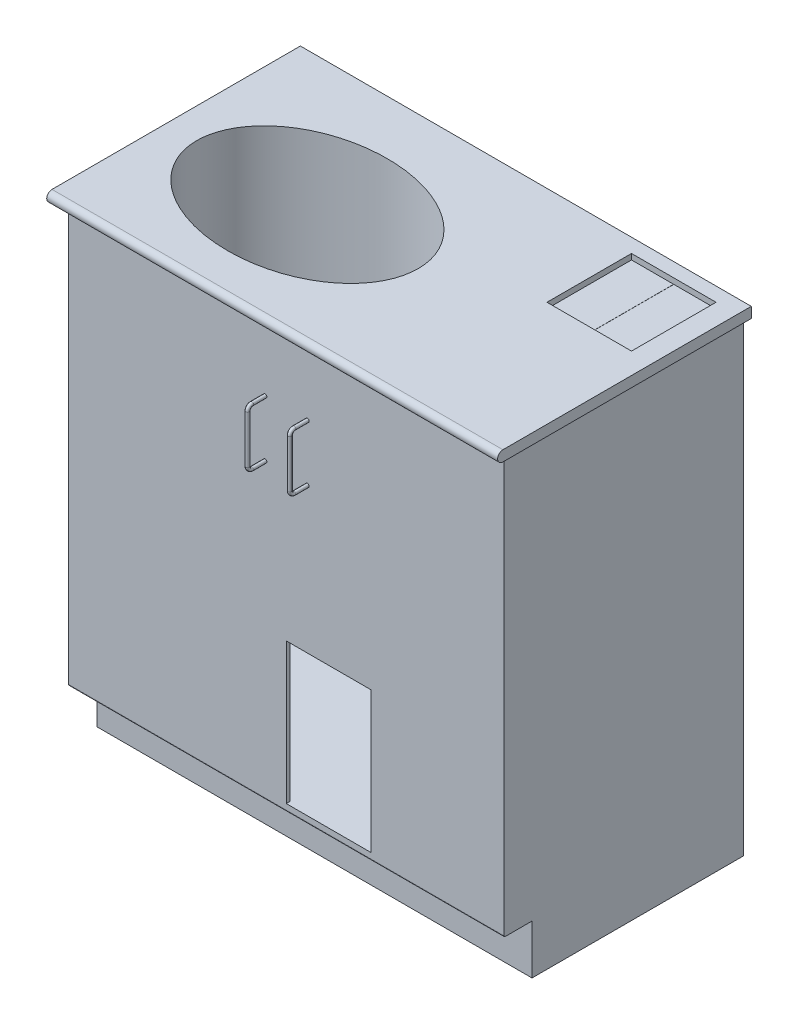
SolidWorks part; units mm, degrees
other "Camera1"
other "Camera2"
ref_plane "Front Plane" through (0, 0, 0) normal (0, 0, 1) x (1, 0, 0)
ref_plane "Top Plane" through (0, 0, 0) normal (0, 1, 0) x (1, 0, 0)
ref_plane "Right Plane" through (0, 0, 0) normal (1, 0, 0) x (0, 0, -1)
ref_plane "Ground Plane" through (0, 0, 0) normal (0, 1, 0) x (1, 0, 0)
sketch "Sketch2" plane through (0, 0, 0) normal (0, 1, 0) x (1, 0, 0)
  line L1 (0, 0) -> (812.8, 0)
  line L2 (0, 0) -> (0, 457.2)
  line L3 (0, 457.2) -> (812.8, 457.2)
  line L4 (812.8, 0) -> (812.8, 457.2)
  dimension "D1" = 812.8
  dimension "D2" = 457.2
extrude "Boss-Extrude1" add sketch "Sketch2" along normal blind 865.124
ref_plane "Wall Plane" through (0, 0, -457.2) normal (0, 0, -1) x (-1, 0, 0)
ref_plane "Faucet Plane" through (254, 0, 0) normal (-1, 0, 0) x (0, 0, 1)
ref_plane "Central Plane" through (406.4, 0, 0) normal (-1, 0, 0) x (0, 0, 1)
ref_plane "Piping Alignment" through (203.2, 0, 0) normal (-1, 0, 0) x (0, 0, 1)
sketch "Sketch28" plane through (0, 0, -457.2) normal (0, 0, -1) x (-1, 0, 0)
  line L1 (-203.2, -251.46) -> (-203.2, 251.46) construction
  circle A0 centre (-203.2, 744.0072) radius 6.35
  dimension "D1" = 0
extrude "Boss-Extrude4" add sketch "Sketch28" along normal blind 50.8
sketch "Sketch30" plane through (0, 0, -457.2) normal (0, 0, -1) x (-1, 0, 0)
  line L1 (-203.2, -251.46) -> (-203.2, 251.46) construction
  circle A0 centre (-203.2, 575.1895) radius 19.05
  dimension "D1" = 0
extrude "Boss-Extrude5" add sketch "Sketch30" along normal blind 50.8
sketch "Sketch31" plane through (812.8, 0, 0) normal (1, 0, 0) x (0, 0, -1)
  line L0 (0, 865.124) -> (0, 0) construction
  line L1 (0, 846.074) -> (25.4, 846.074)
  line L2 (0, 846.074) -> (0, 0)
  line L3 (0, 0) -> (25.4, 0)
  line L4 (25.4, 846.074) -> (25.4, 0)
  line L5 (0, 0) -> (457.2, 0) construction
  line L6 (0, 865.124) -> (457.2, 865.124) construction
  dimension "D1" = 25.4
  dimension "D2" = 19.05
extrude "Cut-Extrude1" cut sketch "Sketch31" against normal through all both and the other way through all
ref_plane "Plane2" through (368.3, 0, 0) normal (-1, 0, 0) x (0, 0, 1)
ref_plane "Plane3" through (444.5, 0, 0) normal (-1, 0, 0) x (0, 0, 1)
sketch "Sketch34" plane through (368.3, 0, 0) normal (-1, 0, 0) x (0, 0, 1)
  line L0 (-25.4, 719.074) -> (-1.27, 719.074)
  line L1 (-25.4, 0) -> (-25.4, 846.074) construction
  line L2 (6.35, 711.454) -> (6.35, 625.094)
  line L3 (-1.27, 617.474) -> (-25.4, 617.474)
  line L4 (-25.4, 846.074) -> (0, 846.074) construction
  arc A0 (-1.27, 719.074) -> (6.35, 711.454) centre (-1.27, 711.454) cw
  arc A1 (6.35, 625.094) -> (-1.27, 617.474) centre (-1.27, 625.094) cw
  dimension "D2" = 7.62
  dimension "D3" = 7.62
  dimension "D1" = 31.75
  dimension "D4" = 101.6
  dimension "D5" = 127
sweep "Sweep2" add path "Sketch34" circular profile diameter 6.35 parameters "D3"=6.35
mirror "Mirror1" about plane through (406.4, 0, 0) normal (-1, 0, 0) of "Sweep2"
fillet "Fillet1" 2 edges at (406.4, 865.124, 0) (406.4, 846.074, 0) type full round first side face at (406.4, 865.124, -228.6) second side face at (406.4, 846.074, -12.7) middle face at (406.4, 855.599, 0)
sketch "Sketch160" plane through (0, 0, -25.4) normal (0, 0, 1) x (1, 0, 0)
  line L0 (0, 846.074) -> (812.8, 846.074) construction
  line L1 (812.8, 0) -> (798.576, 0)
  line L2 (812.8, 0) -> (812.8, 846.074)
  line L3 (812.8, 846.074) -> (798.576, 846.074)
  line L4 (798.576, 0) -> (798.576, 846.074)
  line L5 (0, 0) -> (812.8, 0) construction
  line L6 (0, 846.074) -> (14.224, 846.074)
  line L7 (0, 846.074) -> (0, 0)
  line L8 (0, 0) -> (14.224, 0)
  line L9 (14.224, 846.074) -> (14.224, 0)
  dimension "D1" = 14.224
  dimension "D2" = 14.224
extrude "Cut-Extrude2" cut sketch "Sketch160" against normal through all both and the other way through all
ref_axis "Axis - Drain" through (203.2, 575.1895, -508) along (0, 0, 1)
ref_axis "Axis - Water" through (203.2, 744.0072, -508) along (0, 0, 1)
sketch "Sketch163" plane through (0, 0, -25.4) normal (0, 0, 1) x (1, 0, 0)
  line L0 (14.224, 0) -> (798.576, 0) construction
  line L1 (406.4, 355.6) -> (558.8, 355.6)
  line L2 (406.4, 355.6) -> (406.4, 101.6)
  line L3 (406.4, 101.6) -> (558.8, 101.6)
  line L4 (558.8, 355.6) -> (558.8, 101.6)
  line L5 (812.8, 846.074) -> (812.8, 0) construction
  dimension "D1" = 101.6
  dimension "D2" = 254
  dimension "D3" = 152.4
  dimension "D4" = 254
extrude "Cut-Extrude4" cut sketch "Sketch163" against normal blind 406.4
ref_plane "Plane4" through (0, 0, -31.75) normal (0, 0, 1) x (1, 0, 0)
sketch "Sketch193" plane through (0, 0, -31.75) normal (0, 0, 1) x (1, 0, 0)
  line L0 (798.576, 0) -> (798.576, 846.074) construction
  line L1 (20.574, 101.6) -> (792.226, 101.6)
  line L2 (20.574, 101.6) -> (20.574, 411.9299)
  line L3 (20.574, 411.9299) -> (792.226, 411.9299)
  line L4 (792.226, 101.6) -> (792.226, 411.9299)
  line L5 (14.224, 846.074) -> (14.224, 0) construction
  line L9 (406.4, 101.6) -> (558.8, 101.6) construction
  dimension "D1" = 6.35
  dimension "D2" = 6.35
extrude "Cut-Extrude10" cut sketch "Sketch193" against normal blind 419.1
sketch "Sketch195" plane through (0, 865.124, 0) normal (0, 1, 0) x (1, 0, 0)
  line L0 (812.8, 457.2) -> (0, 457.2) construction
  line L1 (774.7, 431.8) -> (622.3, 431.8)
  line L2 (774.7, 431.8) -> (774.7, 279.4)
  line L3 (774.7, 279.4) -> (622.3, 279.4)
  line L4 (622.3, 431.8) -> (622.3, 279.4)
  line L5 (812.8, 9.525) -> (812.8, 457.2) construction
  dimension "D1" = 152.4
  dimension "D2" = 152.4
  dimension "D3" = 25.4
  dimension "D4" = 38.1
extrude "Cut-Extrude12" cut sketch "Sketch195" against normal blind 659.13
ref_plane "Plane5" through (0, 852.424, 0) normal (0, 1, 0) x (1, 0, 0)
sketch "Sketch196" plane through (0, 852.424, 0) normal (0, 1, 0) x (1, 0, 0)
  line L1 (622.3, 431.8) -> (698.246, 431.8)
  line L2 (622.3, 431.8) -> (622.3, 279.4)
  line L3 (622.3, 279.4) -> (698.246, 279.4)
  line L4 (698.246, 431.8) -> (698.246, 279.4)
  dimension "D1" = 75.946
extrude "Boss-Extrude13" add sketch "Sketch196" along normal blind 2.54
sketch "Sketch197" plane through (0, 852.424, 0) normal (0, 1, 0) x (1, 0, 0)
  line L0 (622.3, 279.4) -> (774.7, 279.4) construction
  line L1 (774.7, 431.8) -> (698.5, 431.8)
  line L2 (774.7, 431.8) -> (774.7, 279.4)
  line L3 (774.7, 279.4) -> (698.5, 279.4)
  line L4 (698.5, 431.8) -> (698.5, 279.4)
extrude "Boss-Extrude14" add sketch "Sketch197" along normal blind 2.54
sketch "Sketch206" plane through (0, 865.124, 0) normal (0, 1, 0) x (1, 0, 0)
  ellipse E0 centre (254, 215.9) end of major axis (54.2175, 215.9) minor radius 143.8906
extrude "Cut-Extrude13" cut sketch "Sketch206" against normal up to next
sketch "Sketch211" plane through (0, 0, -25.4) normal (0, 0, 1) x (1, 0, 0)
  line L0 (798.576, 0) -> (798.576, 846.074) construction
  line L1 (14.224, 0) -> (798.576, 0)
  line L2 (14.224, 0) -> (14.224, 88.9)
  line L3 (14.224, 88.9) -> (798.576, 88.9)
  line L4 (798.576, 0) -> (798.576, 88.9)
  line L5 (406.4, 101.6) -> (558.8, 101.6) construction
  dimension "D1" = 12.7
extrude "Cut-Extrude14" cut sketch "Sketch211" against normal blind 50.8
fillet "Fillet2" radius 2.54 1 edges at (406.4, 88.9, -25.4)
